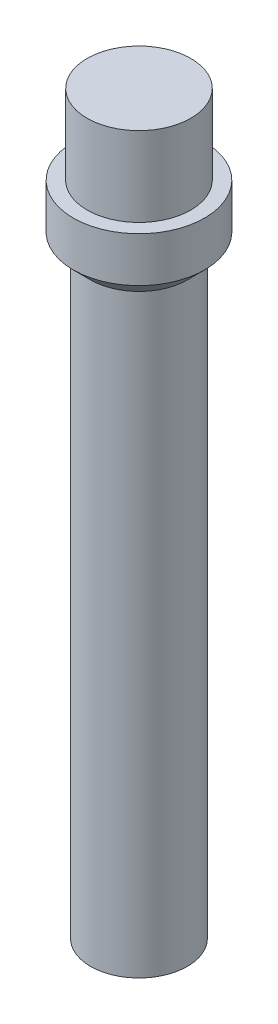
SolidWorks part; units mm, degrees
ref_plane "Front Plane" through (0, 0, 0) normal (0, 0, 1) x (1, 0, 0)
ref_plane "Top Plane" through (0, 0, 0) normal (0, 1, 0) x (1, 0, 0)
ref_plane "Right Plane" through (0, 0, 0) normal (1, 0, 0) x (0, 0, -1)
sketch "Sketch1" plane through (0, 0, 0) normal (0, 1, 0) x (1, 0, 0)
  circle A0 centre (0, 0) radius 1.5
  circle A1 centre (0, 0) radius 1.9
  circle A2 centre (0, 0) radius 1.4
  dimension "D1" = 3
  dimension "D2" = 2.8
  dimension "D3" = 3.8
extrude "Boss-Extrude1" add sketch "Sketch1" along normal blind 2.3 contours A0 A2 | A2 region at (-1.4576, 0, 0) region at (0, 0, 0)
extrude "Boss-Extrude2" add sketch "Sketch1<4>" against normal blind 1.3 contours A2 | A1 A0 | A0 A2 region at (-1.4576, 0, 0) region at (-1.8463, 0, 0) region at (0, 0, 0)
sketch "Sketch1<4>" plane through (0, 0, 0) normal (0, 1, 0) x (1, 0, 0) same geometry as "Sketch1"
extrude "Boss-Extrude3" add sketch "Sketch1<5>" against normal blind 19 contours A2 region at (0, 0, 0)
sketch "Sketch1<5>" plane through (0, 0, 0) normal (0, 1, 0) x (1, 0, 0) same geometry as "Sketch1"
chamfer "Chamfer1" distance 0.5 angle 45 1 edges at (0, -1.3, 1.4)
